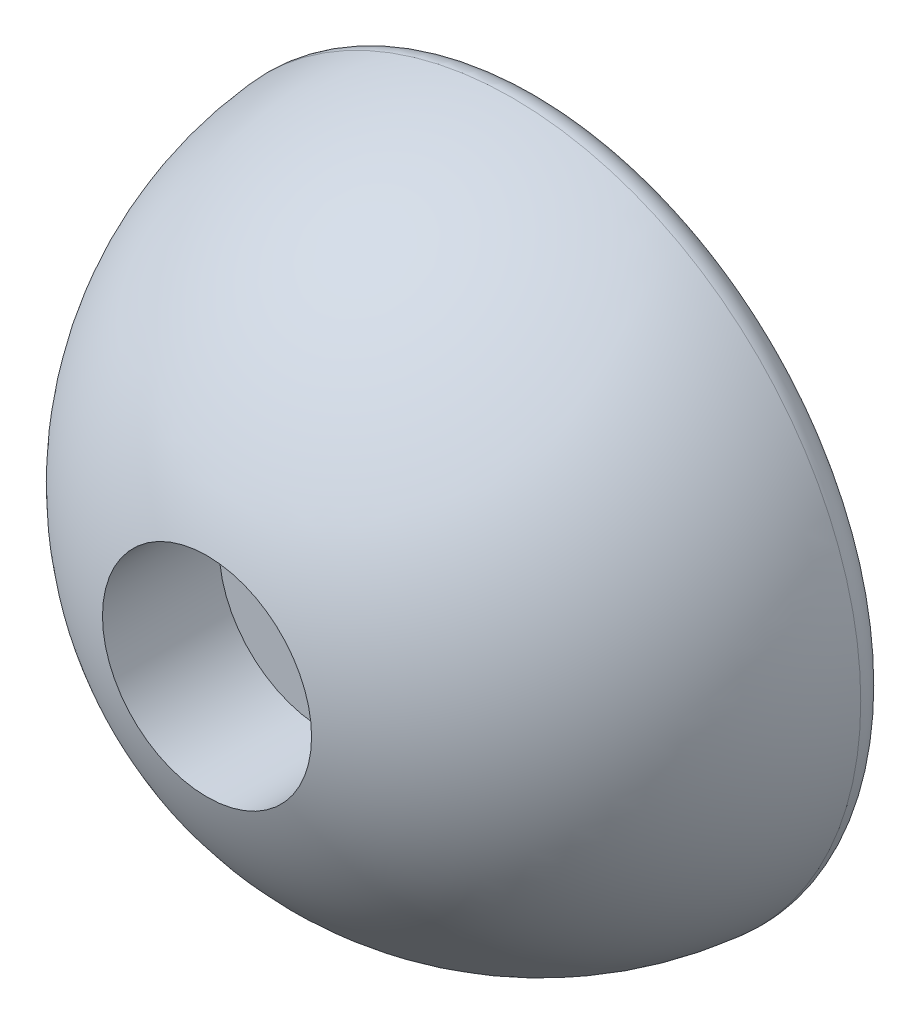
SolidWorks part; units mm, degrees
ref_plane "Front Plane" through (0, 0, 0) normal (0, 0, 1) x (1, 0, 0)
ref_plane "Top Plane" through (0, 0, 0) normal (0, 1, 0) x (1, 0, 0)
ref_plane "Right Plane" through (0, 0, 0) normal (1, 0, 0) x (0, 0, -1)
ref_axis "Polar Axis" through (0, 0, -14.3) along (0, 0, 1)
ref_axis "Solar Axis" through (-14.3, 0, 0) along (1, 0, 0)
sketch "Sketch2" plane through (0, 0, 0) normal (0, 1, 0) x (1, 0, 0)
  line L0 (2.1, 0) -> (5.35, 0)
  line L1 (5.6, 0) -> (9.75, 0) construction
  line L3 (1.6, -5.1051) -> (1.6, -3.3193)
  line L4 (0.92, -3.3193) -> (0.92, -2.1493)
  line L5 (2.1, -0.2) -> (2.1, 0)
  line L7 (0, 0) -> (0, -7) construction
  line L8 (1.6, -6.5906) -> (1.6, -5.3666) construction
  line L9 (1.6, -3.3193) -> (0.92, -3.3193)
  line L10 (1.6, -6.5906) -> (7.1851, -6.5906) construction
  circle A0 centre (0, 0) radius 2 construction
  arc A1 (1.6, -5.1051) -> (5.35, 0) centre (0, 0) ccw
  arc A2 (0.92, -2.1493) -> (2.1, -0.2) centre (-0.1, -0.2) ccw
  arc A3 (1.6, -5.3666) -> (5.6, 0) centre (0, 0) ccw construction
  arc A4 (7.1851, -6.5906) -> (9.75, 0) centre (0, 0) ccw construction
  dimension "D1" = 7
  dimension "D2" = 0.92
  dimension "D3" = 2.1
  dimension "D4" = 10.7
  dimension "D7" = 2.2
  dimension "D8" = 0.2
  dimension "D9" = 4
  dimension "D10" = 0.25
  dimension "D5" = 1.6
  dimension "D6" = 1.17
revolve "Main Body" add sketch "Sketch2" angle 360 about L7
fillet "Bottom Fillet" radius 0.4 2 edges at (-5.35, 0, 0) (-2.1, 0, 0)
fillet "Fillet1" radius 0.6 1 edges at (-0.92, 0, 2.1493)
